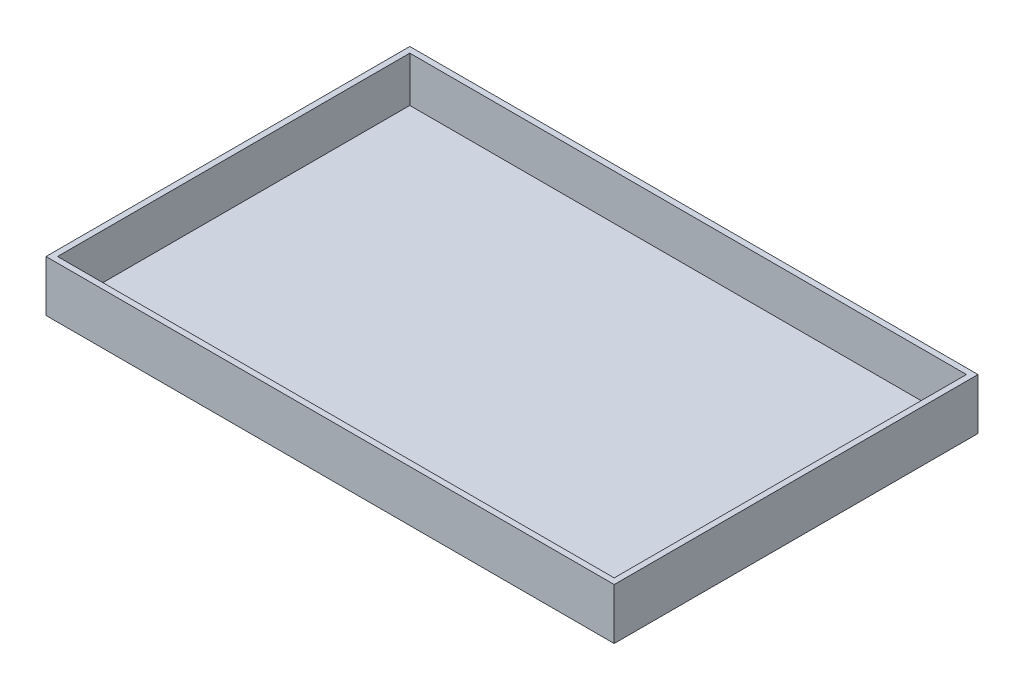
SolidWorks part; units mm, degrees
ref_plane "Front Plane" through (0, 0, 0) normal (0, 0, 1) x (1, 0, 0)
ref_plane "Top Plane" through (0, 0, 0) normal (0, 1, 0) x (1, 0, 0)
ref_plane "Right Plane" through (0, 0, 0) normal (1, 0, 0) x (0, 0, -1)
sketch "Sketch1" plane through (0, 0, 0) normal (0, 1, 0) x (1, 0, 0)
  line L1 (-1249.5, -800) -> (1249.5, -800)
  line L2 (-1249.5, -800) -> (-1249.5, 800)
  line L3 (-1249.5, 800) -> (1249.5, 800)
  line L4 (1249.5, -800) -> (1249.5, 800)
  line L5 (-1249.5, -800) -> (1249.5, 800) construction
  line L6 (-1249.5, 800) -> (1249.5, -800) construction
  point P0 (0, 0)
  dimension "D1" = 1600
  dimension "D2" = 2499
extrude "Boss-Extrude1" add sketch "Sketch1" along normal blind 260
shell "Shell1" thickness 25.4
sketch "Sketch2" plane through (0, 260, 0) normal (0, 1, 0) x (1, 0, 0)
  line L1 (1249.5, -800) -> (-1249.5, -800)
  line L2 (1249.5, -800) -> (1249.5, 800)
  line L3 (1249.5, 800) -> (-1249.5, 800)
  line L4 (-1249.5, -800) -> (-1249.5, 800)
  line L5 (1249.5, -800) -> (-1249.5, 800) construction
  line L6 (1249.5, 800) -> (-1249.5, -800) construction
  point P0 (0, 0)
extrude "Cut-Extrude1" cut sketch "Sketch2" against normal blind 35.306
